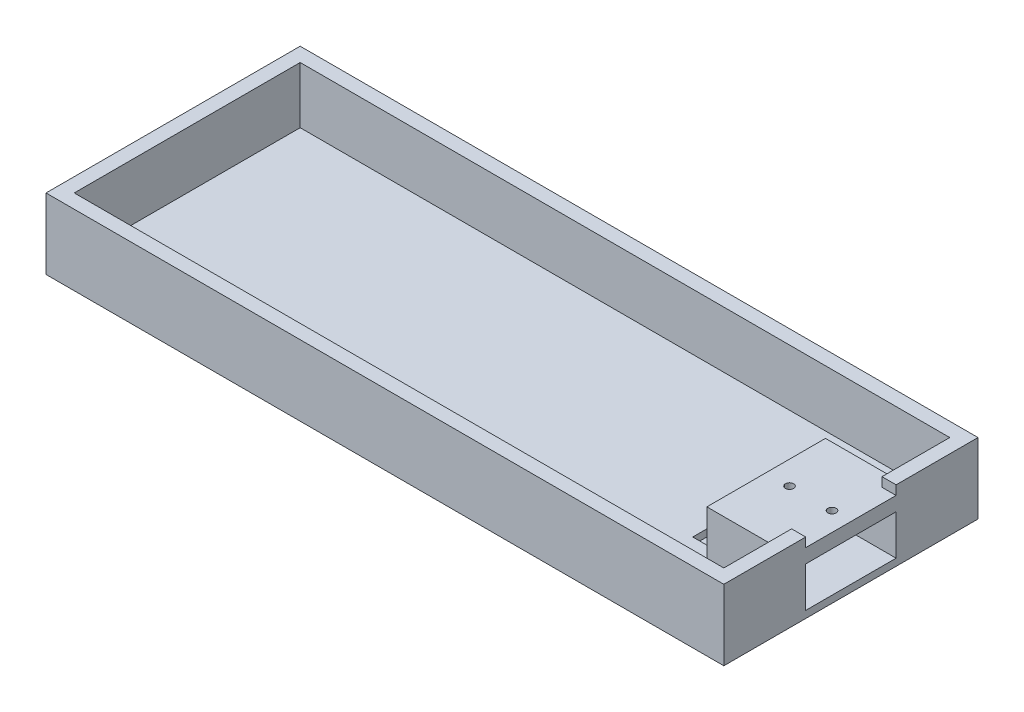
SolidWorks part; units mm, degrees
ref_plane "Front Plane" through (0, 0, 0) normal (0, 0, 1) x (1, 0, 0)
ref_plane "Top Plane" through (0, 0, 0) normal (0, 1, 0) x (1, 0, 0)
ref_plane "Right Plane" through (0, 0, 0) normal (1, 0, 0) x (0, 0, -1)
sketch "Sketch1" plane through (0, 0, 0) normal (0, 1, 0) x (1, 0, 0)
  line L1 (-152.4, -57.15) -> (152.4, -57.15)
  line L2 (-152.4, -57.15) -> (-152.4, 57.15)
  line L3 (-152.4, 57.15) -> (152.4, 57.15)
  line L4 (152.4, -57.15) -> (152.4, 57.15)
  line L5 (-152.4, -57.15) -> (152.4, 57.15) construction
  line L6 (-152.4, 57.15) -> (152.4, -57.15) construction
  point P0 (0, 0)
  dimension "D1" = 304.8
  dimension "D2" = 114.3
extrude "Boss-Extrude1" add sketch "Sketch1" along normal blind 6.35
sketch "Sketch2" plane through (0, 6.35, 0) normal (0, 1, 0) x (1, 0, 0)
  line L0 (152.4, -57.15) -> (152.4, 57.15) construction
  line L1 (-152.4, 57.15) -> (152.4, 57.15)
  line L2 (-152.4, 57.15) -> (-152.4, 50.8)
  line L3 (-152.4, 50.8) -> (152.4, 50.8)
  line L4 (152.4, 57.15) -> (152.4, 50.8)
  line L5 (-152.4, 57.15) -> (-152.4, -57.15) construction
  line L6 (152.4, -57.15) -> (-152.4, -57.15)
  line L7 (152.4, -57.15) -> (152.4, -50.8)
  line L8 (152.4, -50.8) -> (-152.4, -50.8)
  line L9 (-152.4, -57.15) -> (-152.4, -50.8)
  line L11 (-152.4, -50.8) -> (-146.05, -50.8)
  line L12 (-152.4, -50.8) -> (-152.4, 50.8)
  line L13 (-152.4, 50.8) -> (-146.05, 50.8)
  line L14 (-146.05, -50.8) -> (-146.05, 50.8)
  line L15 (152.4, 50.8) -> (146.05, 50.8)
  line L16 (152.4, 50.8) -> (152.4, -50.8)
  line L17 (152.4, -50.8) -> (146.05, -50.8)
  line L18 (146.05, 50.8) -> (146.05, -50.8)
  line M13 (152.4, -57.15) -> (152.4, 57.15)
  line M14 (152.4, 57.15) -> (-152.4, 57.15)
  line M15 (-152.4, 57.15) -> (-152.4, -57.15)
  line M16 (-152.4, -57.15) -> (152.4, -57.15)
  dimension "D1" = 6.35
extrude "Boss-Extrude2" add sketch "Sketch2" along normal blind 25.4 contours L8 L14 L3 M15 | L3 M15 M13 M14 | L3 L18 L8 M13 | L8 M13 M15 M16 region at (0, 6.35, -53.975) region at (-149.225, 6.35, 0) region at (149.225, 6.35, 0) region at (0, 6.35, 53.975)
sketch "Sketch3" plane through (0, 31.75, 0) normal (0, 1, 0) x (1, 0, 0)
  line L0 (146.05, 50.8) -> (146.05, -50.8) construction
  line L1 (146.05, 20.32) -> (152.4, 20.32)
  line L2 (146.05, 20.32) -> (146.05, -20.32)
  line L3 (146.05, -20.32) -> (152.4, -20.32)
  line L4 (152.4, 20.32) -> (152.4, -20.32)
  line L5 (152.4, -57.15) -> (152.4, 57.15) construction
  point P8 (146.05, 0)
  dimension "D1" = 40.64
extrude "Cut-Extrude1" cut sketch "Sketch3" against normal up to surface (25.4 mm away) up to face at (0, 6.35, 0)
sketch "Sketch4" plane through (0, 6.35, 0) normal (0, 1, 0) x (1, 0, 0)
  line L0 (146.05, -20.32) -> (152.4, -20.32) construction
  line L1 (152.4, 20.32) -> (101.6, 20.32)
  line L2 (152.4, 20.32) -> (152.4, -20.32)
  line L3 (152.4, -20.32) -> (101.6, -20.32)
  line L4 (101.6, 20.32) -> (101.6, -20.32)
  dimension "D1" = 50.8
extrude "Cut-Extrude2" cut sketch "Sketch4" against normal blind 3.175
sketch "Sketch5" plane through (0, 6.35, 0) normal (0, 1, 0) x (1, 0, 0)
  line L1 (146.05, 20.32) -> (114.3, 20.32)
  line L2 (146.05, 20.32) -> (146.05, 26.67)
  line L3 (146.05, 26.67) -> (114.3, 26.67)
  line L4 (114.3, 20.32) -> (114.3, 26.67)
  dimension "D1" = 31.75
  dimension "D2" = 6.35
extrude "Boss-Extrude3" add sketch "Sketch5" along normal up to surface (14.913 mm away)
sketch "Sketch6" plane through (0, 21.263, 0) normal (0, 1, 0) x (1, 0, 0)
  line L1 (114.3, 26.67) -> (152.4, 26.67)
  line L2 (114.3, 26.67) -> (114.3, 0)
  line L3 (114.3, 0) -> (152.4, 0)
  line L4 (152.4, 26.67) -> (152.4, 0)
  line L5 (152.4, 20.32) -> (152.4, 57.15) construction
extrude "Boss-Extrude4" add sketch "Sketch6" along normal blind 6.35
mirror "Mirror1" about plane through (0, 0, 0) normal (0, 0, 1) of "Boss-Extrude4", "Boss-Extrude3"
sketch "Sketch7" plane through (0, 27.613, 0) normal (0, 1, 0) x (1, 0, 0)
  circle A0 centre (124.8, 0) radius 1.85 construction
  circle A1 centre (143.9, 0) radius 1.85 construction
  circle A2 centre (124.8, 0) radius 1.85
  circle A3 centre (143.9, 0) radius 1.85
extrude "Cut-Extrude3" cut sketch "Sketch7" against normal up to next
